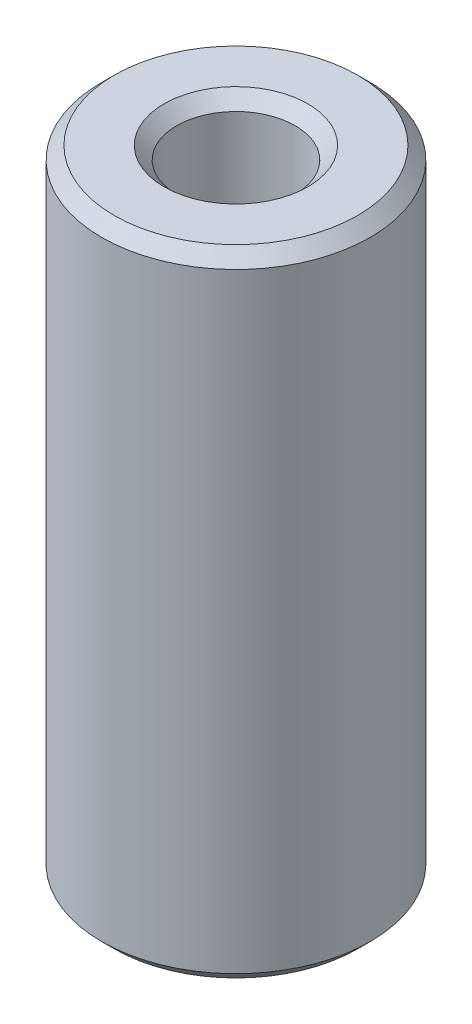
SolidWorks part; units mm, degrees
ref_plane "Front Plane" through (0, 0, 0) normal (0, 0, 1) x (1, 0, 0)
ref_plane "Top Plane" through (0, 0, 0) normal (0, 1, 0) x (1, 0, 0)
ref_plane "Right Plane" through (0, 0, 0) normal (1, 0, 0) x (0, 0, -1)
sketch "Sketch1" plane through (0, 0, 0) normal (0, 1, 0) x (1, 0, 0)
  circle A0 centre (0, 0) radius 30
  dimension "SLEEVE_OD" = 60
extrude "Boss-Extrude1" add sketch "Sketch1" along normal blind 141.9065
sketch "Sketch2" plane through (0, 0, 0) normal (0, 1, 0) x (1, 0, 0)
  circle A0 centre (0, 0) radius 13.2475
  dimension "BORE_D" = 26.4951
extrude "Cut-Extrude1" cut sketch "Sketch2" along normal through all
chamfer "Chamfer1" distance 2.8209 angle 45 4 edges at (0, 141.9065, 13.2475) (0, 0, 13.2475) (0, 0, 30) (0, 141.9065, 30)
